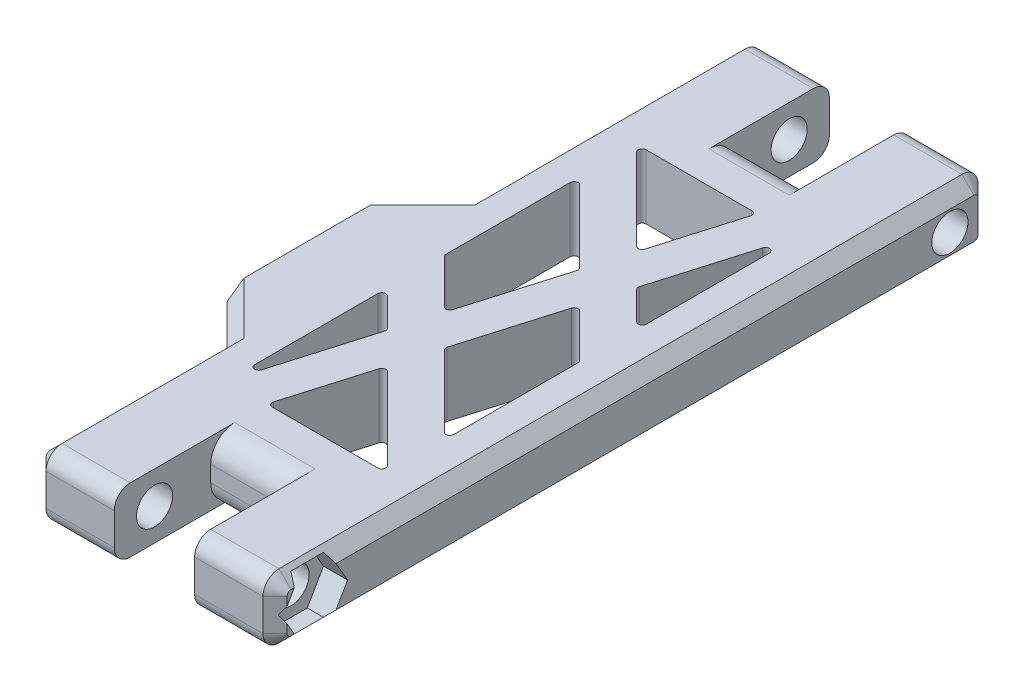
SolidWorks part; units mm, degrees
ref_plane "Front Plane" through (0, 0, 0) normal (0, 0, 1) x (1, 0, 0)
ref_plane "Top Plane" through (0, 0, 0) normal (0, 1, 0) x (1, 0, 0)
ref_plane "Right Plane" through (0, 0, 0) normal (1, 0, 0) x (0, 0, -1)
sketch "Sketch1" plane through (0, 0, 0) normal (0, 1, 0) x (1, 0, 0)
  line L1 (-15, 44.5) -> (15, 44.5)
  line L2 (-15, 44.5) -> (-15, -44.5)
  line L3 (-15, -44.5) -> (15, -44.5)
  line L4 (15, 44.5) -> (15, -44.5)
  line L5 (-15, 44.5) -> (15, -44.5) construction
  line L6 (-15, -44.5) -> (15, 44.5) construction
  point P0 (0, 0)
  dimension "D1" = 30
  dimension "D2" = 89
extrude "Boss-Extrude1" add sketch "Sketch1" along normal blind 8
sketch "Sketch2" plane through (0, 8, 0) normal (0, 1, 0) x (1, 0, 0)
  line L0 (15, 44.5) -> (-15, 44.5) construction
  line L1 (-5, 44.5) -> (5, 44.5)
  line L2 (-5, 44.5) -> (-5, 32.5)
  line L3 (-5, 32.5) -> (5, 32.5)
  line L4 (5, 44.5) -> (5, 32.5)
  line L5 (-15, -44.5) -> (15, -44.5) construction
  line L6 (5, -44.5) -> (-5, -44.5)
  line L7 (5, -44.5) -> (5, -32.5)
  line L8 (5, -32.5) -> (-5, -32.5)
  line L9 (-5, -44.5) -> (-5, -32.5)
  line L10 (15, -44.5) -> (15, 44.5) construction
  dimension "D1" = 10
  dimension "D2" = 10
  dimension "D3" = 10
  dimension "D4" = 12
  dimension "D5" = 12
  dimension "D6" = 10
extrude "Cut-Extrude1" cut sketch "Sketch2" against normal blind 8
sketch "Sketch3" plane through (15, 0, 0) normal (1, 0, 0) x (0, 0, -1)
  line L0 (-44.5, 8) -> (-44.5, 0) construction
  line L1 (-44.5, 8) -> (44.5, 8) construction
  circle A0 centre (-39.5, 4) radius 2.25
  dimension "D1" = 4.5
  dimension "D2" = 5
  dimension "D3" = 4
extrude "Cut-Extrude2" cut sketch "Sketch3" against normal through all
mirror "Mirror1" about plane through (0, 0, 0) normal (0, 0, 1) of "Cut-Extrude2"
fillet "Fillet1" radius 2 8 edges at (10, 0, -44.5) (10, 8, -44.5) (-10, 8, -44.5) (-10, 0, -44.5) (-10, 8, 44.5) (-10, 0, 44.5) (10, 0, 44.5) (10, 8, 44.5)
sketch "Sketch4" plane through (0, 8, 0) normal (0, 1, 0) x (1, 0, 0)
  line L0 (5, 25.5) -> (-10, 25.5)
  line L1 (-10, 25.5) -> (1.5909, 13.9091)
  line L2 (10, 5.5) -> (10, 25.5)
  line L3 (-10, -5.5) -> (-10, -25.5)
  line L4 (-5, -25.5) -> (10, -25.5)
  line L5 (10, -25.5) -> (-1.5909, -13.9091)
  line L6 (15, -42.5) -> (15, 42.5) construction
  line L7 (-15, 42.5) -> (-15, -42.5) construction
  line L8 (-10, 18.4289) -> (-10, 1.5711)
  line L9 (-10, 1.5711) -> (-3.8475, -4.5814)
  line L10 (9.9156, -18.3446) -> (9.9156, -1.4867)
  line L11 (9.9156, -1.4867) -> (3.8475, 4.5814)
  line L12 (-5, 32.5) -> (5, 32.5) construction
  line L13 (5, -32.5) -> (-5, -32.5) construction
  line L14 (5, 25.5) -> (1.5909, 13.9091)
  line L15 (-5, -25.5) -> (-1.5909, -13.9091)
  line L16 (0.0162, -8.4451) -> (3.8475, 4.5814)
  line L18 (5.4545, 10.0455) -> (10, 5.5)
  line L19 (-0.0162, 8.4451) -> (-10, 18.4289)
  line L20 (0.0162, -8.4451) -> (9.9156, -18.3446)
  line L21 (-5.4545, -10.0455) -> (-10, -5.5)
  line L22 (-5.4545, -10.0455) -> (-10, -25.5)
  line L23 (-0.0162, 8.4451) -> (-3.8475, -4.5814)
  line L24 (5.4545, 10.0455) -> (10, 25.5)
  dimension "D1" = 5
  dimension "D2" = 5
  dimension "D3" = 5
  dimension "D4" = 45
  dimension "D5" = 45
  dimension "D6" = 5
  dimension "D7" = 5
  dimension "D8" = 7
  dimension "D9" = 7
  dimension "D10" = 20
  dimension "D11" = 20
  dimension "D12" = 15
  dimension "D13" = 14
extrude "Cut-Extrude3" cut sketch "Sketch4" against normal through all
fillet "Fillet2" radius 3 4 edges at (0, 8, -32.5) (0, 8, 32.5) (0, 0, 32.5) (0, 0, -32.5)
sketch "Sketch5" plane through (-15, 0, 0) normal (-1, 0, 0) x (0, 0, 1)
  line L0 (-42.5, 0) -> (42.5, 0) construction
  line L1 (15.5, 0) -> (-4.5, 0)
  line L2 (15.5, 0) -> (15.5, 8)
  line L3 (15.5, 8) -> (-4.5, 8)
  line L4 (-4.5, 0) -> (-4.5, 8)
  line L5 (-42.5, 8) -> (42.5, 8) construction
  line L6 (-44.5, 6) -> (-44.5, 2) construction
  dimension "D1" = 40
  dimension "D2" = 20
extrude "Boss-Extrude2" add sketch "Sketch5" along normal blind 5
sketch "Sketch6" plane through (-20, 0, 0) normal (-1, 0, 0) x (0, 0, 1)
  line L0 (-4.5, 0) -> (15.5, 0) construction
  line L1 (-4.5, 8) -> (-4.5, 0) construction
  circle A0 centre (5.5, 4) radius 1.9
  dimension "D1" = 3.8
  dimension "D2" = 4
  dimension "D3" = 10
extrude "Cut-Extrude4" cut sketch "Sketch6" against normal blind 5
chamfer "Chamfer1" distance 5 angle 45 2 edges at (-15, 4, 15.5) (-15, 4, -4.5)
chamfer "Chamfer2" distance 1.5 angle 45 18 edges at (-15, 0, -26) (-15, 0.5858, -43.9142) (-15, 4, -44.5) (-15, 7.4142, -43.9142) (-15, 8, -26) (-15, 0, 31.5) (-15, 0.5858, 43.9142) (-15, 4, 44.5) (-15, 7.4142, 43.9142) (-15, 8, 31.5) (15, 0, 0) (15, 0.5858, 43.9142) (15, 0.5858, -43.9142) (15, 4, 44.5) (15, 4, -44.5) (15, 7.4142, 43.9142) (15, 7.4142, -43.9142) (15, 8, 0)
fillet "Fillet4" radius 0.5 20 edges at (10, 4, 25.5) (-1.5909, 4, 13.9091) (-5, 4, 25.5) (-5.4545, 4, 10.0455) (-10, 4, 5.5) (-10, 4, 25.5) (9.9156, 4, 18.3446) (9.9156, 4, 1.4867) (3.8475, 4, -4.5814) (0.0162, 4, 8.4451) (-3.8475, 4, 4.5814) (-10, 4, -1.5711) (-0.0162, 4, -8.4451) (-10, 4, -18.4289) (-10, 4, -25.5) (5.4545, 4, -10.0455) (10, 4, -5.5) (10, 4, -25.5) (1.5909, 4, -13.9091) (5, 4, -25.5)
chamfer "Chamfer3" distance 1.5 angle 45 4 edges at (-16.75, 0, 18.75) (-16.75, 8, 18.75) (-16.75, 8, -7.75) (-16.75, 0, -7.75)
sketch "Sketch7" plane through (15, 0, 0) normal (1, 0, 0) x (0, 0, -1)
  line L1 (-35.4585, 4) -> (-37.4793, 7.5)
  line L2 (-37.4793, 7.5) -> (-41.5207, 7.5)
  line L3 (-41.5207, 7.5) -> (-43.5415, 4)
  line L4 (-43.5415, 4) -> (-41.5207, 0.5)
  line L5 (-41.5207, 0.5) -> (-37.4793, 0.5)
  line L6 (-37.4793, 0.5) -> (-35.4585, 4)
  circle A0 centre (-39.5, 4) radius 3.5 construction
  dimension "D1" = 7
extrude "Cut-Extrude5" cut sketch "Sketch7" against normal blind 3
